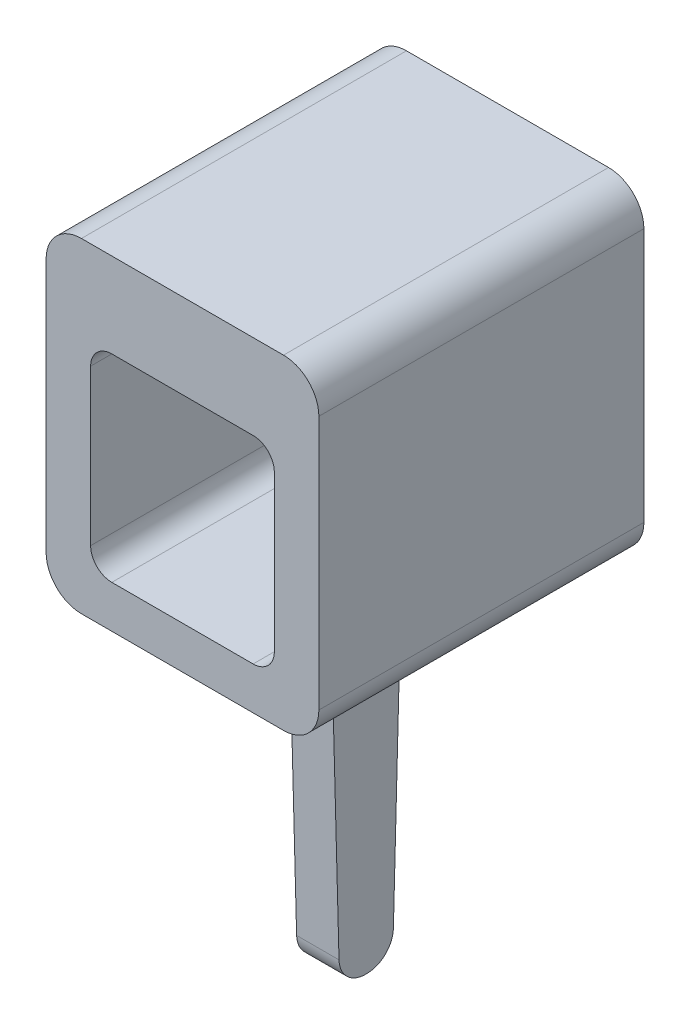
SolidWorks part; units mm, degrees
ref_plane "Спереди" through (0, 0, 0) normal (0, 0, 1) x (1, 0, 0)
ref_plane "Сверху" through (0, 0, 0) normal (0, 1, 0) x (1, 0, 0)
ref_plane "Справа" through (0, 0, 0) normal (1, 0, 0) x (0, 0, -1)
sketch "Эскиз1" plane through (0, 0, 0) normal (0, 1, 0) x (1, 0, 0)
  line L1 (-1.93, 2.3) -> (1.93, 2.3)
  line L2 (-1.93, 2.3) -> (-1.93, -2.3)
  line L3 (-1.93, -2.3) -> (1.93, -2.3)
  line L4 (1.93, 2.3) -> (1.93, -2.3)
  dimension "D1" = 4.6
  dimension "D2" = 3.86
  dimension "D3" = 1.93
  dimension "D4" = 2.3
extrude "Бобышка-Вытянуть1" add sketch "Эскиз1" along normal blind 4.6
sketch "Эскиз2" plane through (0, 0, 2.3) normal (0, 0, 1) x (1, 0, 0)
  line L0 (-1.93, 0) -> (1.93, 0) construction
  line L1 (-1.3, 3.4) -> (1.3, 3.4)
  line L2 (-1.3, 3.4) -> (-1.3, 0.6)
  line L3 (-1.3, 0.6) -> (1.3, 0.6)
  line L4 (1.3, 3.4) -> (1.3, 0.6)
  dimension "D1" = 2.8
  dimension "D2" = 2.6
  dimension "D3" = 0.6
  dimension "D4" = 1.3
extrude "Вырез-Вытянуть1" cut sketch "Эскиз2" against normal through all
fillet "Скругление1" radius 0.5 4 edges at (1.93, 0, 0) (-1.93, 0, 0) (1.93, 4.6, 0) (-1.93, 4.6, 0)
fillet "Скругление2" radius 0.3 4 edges at (1.3, 3.4, 0) (-1.3, 3.4, 0) (-1.3, 0.6, 0) (1.3, 0.6, 0)
sketch "Эскиз3" plane through (0, 0, 0) normal (0, -1, 0) x (1, 0, 0)
  line L1 (-0.3, 0.5) -> (0.3, 0.5)
  line L2 (-0.3, 0.5) -> (-0.3, -0.5)
  line L3 (-0.3, -0.5) -> (0.3, -0.5)
  line L4 (0.3, 0.5) -> (0.3, -0.5)
  dimension "D1" = 0.6
  dimension "D2" = 1
  dimension "D3" = 0.5
  dimension "D4" = 0.3
extrude "Бобышка-Вытянуть2" add sketch "Эскиз3" along normal blind 4.7
chamfer "Фаска1" distance 4.7 distance2 0.125 2 edges at (0, -4.7, 0.5) (0, -4.7, -0.5) first distance on face at (0, -2.35, 0.5) first distance on face at (0, -2.35, -0.5)
fillet "Скругление4" radius 0.375 2 edges at (0, -4.7, -0.375) (0, -4.7, 0.375)
